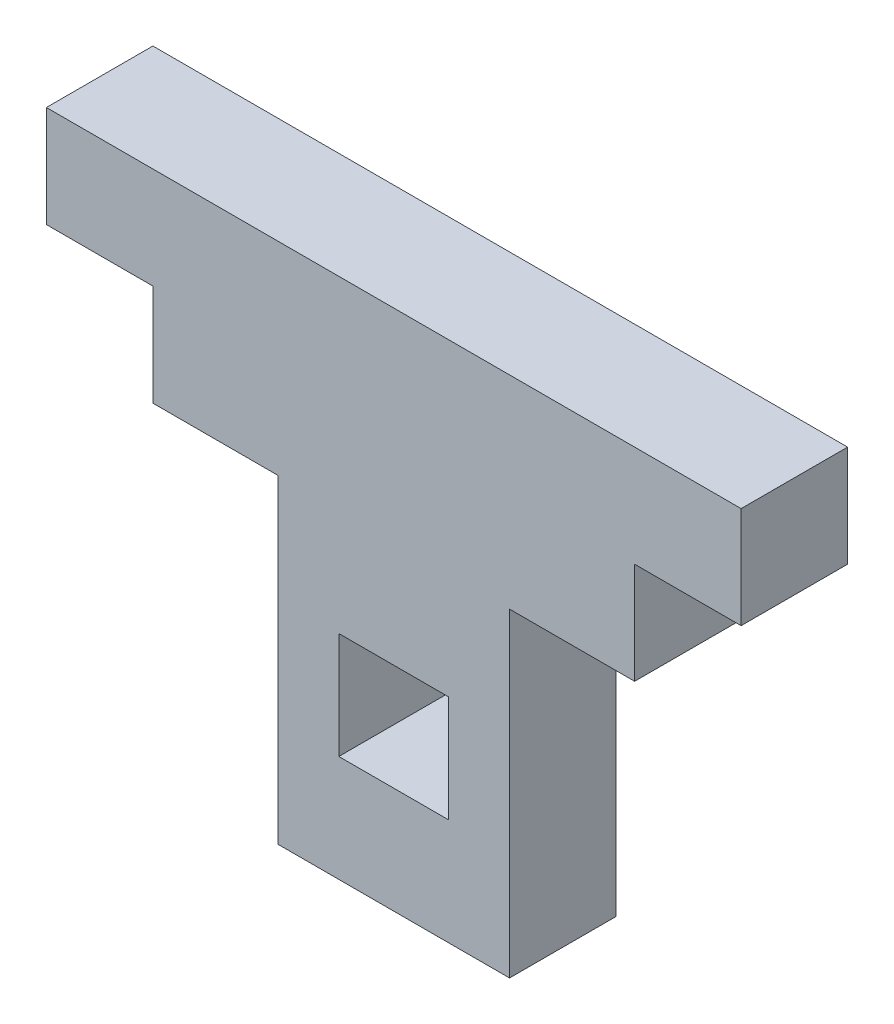
SolidWorks part; units mm, degrees
ref_plane "Front Plane" through (0, 0, 0) normal (0, 0, 1) x (1, 0, 0)
ref_plane "Top Plane" through (0, 0, 0) normal (0, 1, 0) x (1, 0, 0)
ref_plane "Right Plane" through (0, 0, 0) normal (1, 0, 0) x (0, 0, -1)
sketch "Sketch1" plane through (0, 0, 0) normal (0, 0, 1) x (1, 0, 0)
  line L5 (0, 0) -> (24.13, 0)
  line L6 (0, 0) -> (0, 10.16)
  line L7 (0, 10.16) -> (24.13, 10.16)
  line L8 (24.13, 0) -> (24.13, 10.16)
  dimension "D1" = 24.13
  dimension "D2" = 10.16
extrude "Boss-Extrude1" add sketch "Sketch1" along normal blind 5.334 contours L6 L5 L8 L7
sketch "Sketch6" plane through (24.13, 0, 0) normal (1, 0, 0) x (0, 0, -1)
  line L9 (-5.334, 0) -> (-5.334, 10.16) construction
  line L10 (-5.334, 10.16) -> (0, 10.16)
  line L11 (-5.334, 10.16) -> (-5.334, 0)
  line L12 (-5.334, 0) -> (0, 0)
  line L13 (0, 10.16) -> (0, 0)
  line L14 (-5.334, 10.16) -> (0, 10.16) construction
extrude "Boss-Extrude5" add sketch "Sketch6" along normal blind 5.334
sketch "Sketch11" plane through (0, 0, 0) normal (-1, 0, 0) x (0, 0, 1)
  line L1 (0, 10.2062) -> (5.334, 10.2062)
  line L2 (0, 10.2062) -> (0, 0)
  line L3 (0, 0) -> (5.334, 0)
  line L4 (5.334, 10.2062) -> (5.334, 0)
extrude "Boss-Extrude6" add sketch "Sketch11" along normal blind 5.334
sketch "Sketch12" plane through (0, 0, 0) normal (0, -1, 0) x (-1, 0, 0)
  line L1 (-29.464, 0) -> (5.334, 0)
  line L2 (-29.464, 0) -> (-29.464, -5.334)
  line L3 (-29.464, -5.334) -> (5.334, -5.334)
  line L4 (5.334, 0) -> (5.334, -5.334)
extrude "Boss-Extrude7" add sketch "Sketch12" along normal blind 5.334
sketch "Sketch13" plane through (0, 0, 0) normal (0, 0, -1) x (-1, 0, 0)
  line L0 (0, 10.16) -> (5.334, 10.16)
  line L1 (5.334, 10.2062) -> (5.334, -5.334) construction
  line L2 (0, 10.16) -> (0, 10.2062)
  line L3 (5.334, 10.2062) -> (0, 10.2062) construction
  line L4 (0, 10.2062) -> (5.334, 10.2062)
  line L5 (5.334, 10.2062) -> (5.334, 10.16)
extrude "Cut-Extrude1" cut sketch "Sketch13" against normal through all
sketch "Sketch17" plane through (0, -5.334, 0) normal (0, -1, 0) x (-1, 0, 0)
  line L0 (-29.464, -5.334) -> (5.334, -5.334) construction
  line L1 (5.334, 0) -> (-6.2653, 0)
  line L2 (5.334, 0) -> (5.334, -5.334)
  line L3 (5.334, -5.334) -> (-6.2653, -5.334)
  line L4 (-6.2653, 0) -> (-6.2653, -5.334)
  line L5 (-17.8647, 0) -> (-6.2653, 0) construction
  line L6 (-29.464, 0) -> (-17.8647, 0)
  line L7 (-29.464, 0) -> (-29.464, -5.334)
  line L8 (-29.464, -5.334) -> (-17.8647, -5.334)
  line L9 (-17.8647, 0) -> (-17.8647, -5.334)
extrude "Cut-Extrude5" cut sketch "Sketch17" against normal blind 5.334
sketch "Sketch18" plane through (0, 0, 5.334) normal (0, 0, 1) x (1, 0, 0)
  line L0 (17.78, 63.5) -> (17.78, 5.08) construction
  line L1 (-5.334, 10.16) -> (0, 10.16)
  line L2 (-5.334, 10.16) -> (-5.334, 5.08)
  line L3 (-5.334, 5.08) -> (0, 5.08)
  line L4 (0, 10.16) -> (0, 5.08)
  line L5 (17.78, 5.08) -> (29.464, 5.08)
  line L6 (17.78, 5.08) -> (17.78, 10.16)
  line L7 (17.78, 10.16) -> (29.464, 10.16)
  line L8 (29.464, 5.08) -> (29.464, 10.16)
extrude "Cut-Extrude6" cut sketch "Sketch18" against normal blind 5.334
sketch "Sketch19" plane through (17.78, 0, 0) normal (1, 0, 0) x (0, 0, -1)
  line L1 (-5.334, 10.16) -> (0, 10.16)
  line L2 (-5.334, 10.16) -> (-5.334, 5.08)
  line L3 (-5.334, 5.08) -> (0, 5.08)
  line L4 (0, 10.16) -> (0, 5.08)
extrude "Boss-Extrude8" add sketch "Sketch19" along normal blind 5.334
sketch "Sketch20" plane through (23.114, 0, 0) normal (1, 0, 0) x (0, 0, -1)
  line L1 (-5.334, 10.16) -> (0, 10.16)
  line L2 (-5.334, 10.16) -> (-5.334, 5.08)
  line L3 (-5.334, 5.08) -> (0, 5.08)
  line L4 (0, 10.16) -> (0, 5.08)
extrude "Boss-Extrude10" add sketch "Sketch20" along normal blind 1.016
sketch "Sketch21" plane through (0, -5.334, 0) normal (0, -1, 0) x (1, 0, 0)
  line L1 (6.2653, 5.334) -> (17.8647, 5.334)
  line L2 (6.2653, 5.334) -> (6.2653, 0)
  line L3 (6.2653, 0) -> (17.8647, 0)
  line L4 (17.8647, 5.334) -> (17.8647, 0)
extrude "Boss-Extrude11" add sketch "Sketch21" along normal blind 10.668
sketch "Sketch22" plane through (0, 0, 5.334) normal (0, 0, 1) x (1, 0, 0)
  line L0 (17.8647, -16.002) -> (6.2653, -16.002) construction
  line L1 (9.3133, -5.334) -> (14.8167, -5.334)
  line L2 (9.3133, -5.334) -> (9.3133, -10.668)
  line L3 (9.3133, -10.668) -> (14.8167, -10.668)
  line L4 (14.8167, -5.334) -> (14.8167, -10.668)
  line L5 (17.8647, 0) -> (17.8647, -16.002) construction
  line L6 (6.2653, 0) -> (6.2653, -16.002) construction
  dimension "D1" = 5.334
  dimension "D2" = 5.334
  dimension "D3" = 3.048
  dimension "D4" = 3.048
extrude "Cut-Extrude7" cut sketch "Sketch22" against normal through all
sketch "Sketch23" plane through (0, 0, 0) normal (-1, 0, 0) x (0, 0, 1)
  line L1 (0, 5.08) -> (5.334, 5.08)
  line L2 (0, 5.08) -> (0, 10.16)
  line L3 (0, 10.16) -> (5.334, 10.16)
  line L4 (5.334, 5.08) -> (5.334, 10.16)
extrude "Boss-Extrude12" add sketch "Sketch23" along normal blind 5.334
sketch "Sketch24" plane through (-5.334, 0, 0) normal (-1, 0, 0) x (0, 0, 1)
  line L0 (5.334, 0) -> (0, 0) construction
  line L1 (5.334, 0) -> (0, 0)
  line L2 (5.334, 0) -> (5.334, 5.08)
  line L3 (5.334, 5.08) -> (0, 5.08)
  line L4 (0, 0) -> (0, 5.08)
  line L5 (0, 10.16) -> (0, 0) construction
  dimension "D1" = 5.08
extrude "Cut-Extrude8" cut sketch "Sketch24" against normal blind 5.334
sketch "Sketch25" plane through (24.13, 0, 0) normal (1, 0, 0) x (0, 0, -1)
  line L1 (-5.334, 10.16) -> (0, 10.16)
  line L2 (-5.334, 10.16) -> (-5.334, 5.08)
  line L3 (-5.334, 5.08) -> (0, 5.08)
  line L4 (0, 10.16) -> (0, 5.08)
extrude "Boss-Extrude13" add sketch "Sketch25" along normal blind 5.334
sketch "Sketch26" plane through (29.464, 0, 0) normal (1, 0, 0) x (0, 0, -1)
  line L0 (0, 0) -> (0, 10.16) construction
  line L1 (-5.334, 0) -> (0, 0)
  line L2 (-5.334, 0) -> (-5.334, 5.08)
  line L3 (-5.334, 5.08) -> (0, 5.08)
  line L4 (0, 0) -> (0, 5.08)
  dimension "D1" = 5.08
extrude "Cut-Extrude9" cut sketch "Sketch26" against normal blind 5.334
equation "\"Foamcore\" = .1875in"
equation "\"Mdf\"= .21in"
equation "\"Gmaterial\"= \"Mdf\""
equation "\"D1@Boss-Extrude1\"= \"Gmaterial\""
equation "\"D1@Boss-Extrude7\"= \"Gmaterial\""
equation "\"D1@Boss-Extrude6\"= \"Gmaterial\""
equation "\"D1@Boss-Extrude5\"= \"Gmaterial\""
equation "\"D1@Cut-Extrude5\"=\"Gmaterial\""
equation "\"D1@Cut-Extrude6\"=\"Gmaterial\""
equation "\"D1@Boss-Extrude8\"=\"Gmaterial\""
